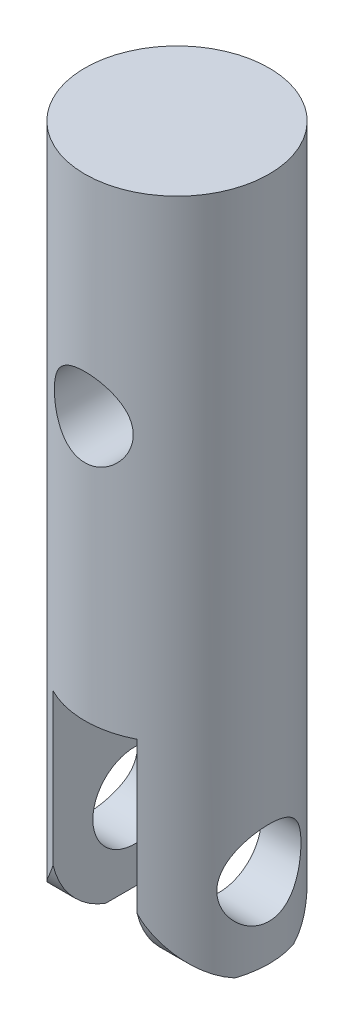
SolidWorks part; units mm, degrees
ref_plane "Front Plane" through (0, 0, 0) normal (0, 0, 1) x (1, 0, 0)
ref_plane "Top Plane" through (0, 0, 0) normal (0, 1, 0) x (1, 0, 0)
ref_plane "Right Plane" through (0, 0, 0) normal (1, 0, 0) x (0, 0, -1)
sketch "Sketch1" plane through (0, 0, 0) normal (0, 1, 0) x (1, 0, 0)
  circle A0 centre (0, 0) radius 8.75
  dimension "D1" = 17.5
extrude "Boss-Extrude1" add sketch "Sketch1" along normal blind 45
sketch "Sketch2" plane through (0, 0, 0) normal (0, -1, 0) x (1, 0, 0)
  line L7 (-4, -7.7822) -> (-4, 7.7822)
  line L9 (4, -7.7822) -> (4, 7.7822)
  arc A0 (-4, 7.7822) -> (-4, -7.7822) centre (0, 0) ccw
  circle A1 centre (0, 0) radius 8.75 construction
  arc A2 (4, -7.7822) -> (4, 7.7822) centre (0, 0) ccw
  point P0 (0, 0)
  point P1 (0, 0)
  dimension "D1" = 8
extrude "Boss-Extrude2" add sketch "Sketch2" along normal blind 20
sketch "Sketch3" plane through (0, 0, 0) normal (1, 0, 0) x (0, 0, -1)
  line L0 (7.7822, 0) -> (-7.7822, 0) construction
  line L3 (-8, -12.5) -> (-11.9447, -12.5)
  line L4 (-11.9447, -12.5) -> (-11.9447, -23.5653)
  line L5 (-11.9447, -23.5653) -> (12.07, -23.5653)
  line L6 (12.07, -23.5653) -> (12.07, -12.5)
  line L7 (12.07, -12.5) -> (8, -12.5)
  circle A0 centre (0, -12.5) radius 4
  arc A1 (-8, -12.5) -> (8, -12.5) centre (0, -12.5) ccw
  dimension "D3" = 8
  dimension "D4" = 16
  dimension "D1" = 12.5
  dimension "D2" = 0
extrude "Cut-Extrude2" cut sketch "Sketch3" against normal blind 15 and the other way blind 15
sketch "Sketch4" plane through (0, 0, 0) normal (0, 0, 1) x (1, 0, 0)
  line L0 (0, 45) -> (0, 25)
  line L1 (8.75, 45) -> (-8.75, 45) construction
  circle A0 centre (0, 25) radius 3.75
  dimension "D1" = 7.5
  dimension "D2" = 20
extrude "Cut-Extrude3" cut sketch "Sketch4" against normal blind 15 and the other way blind 15 contours A0
